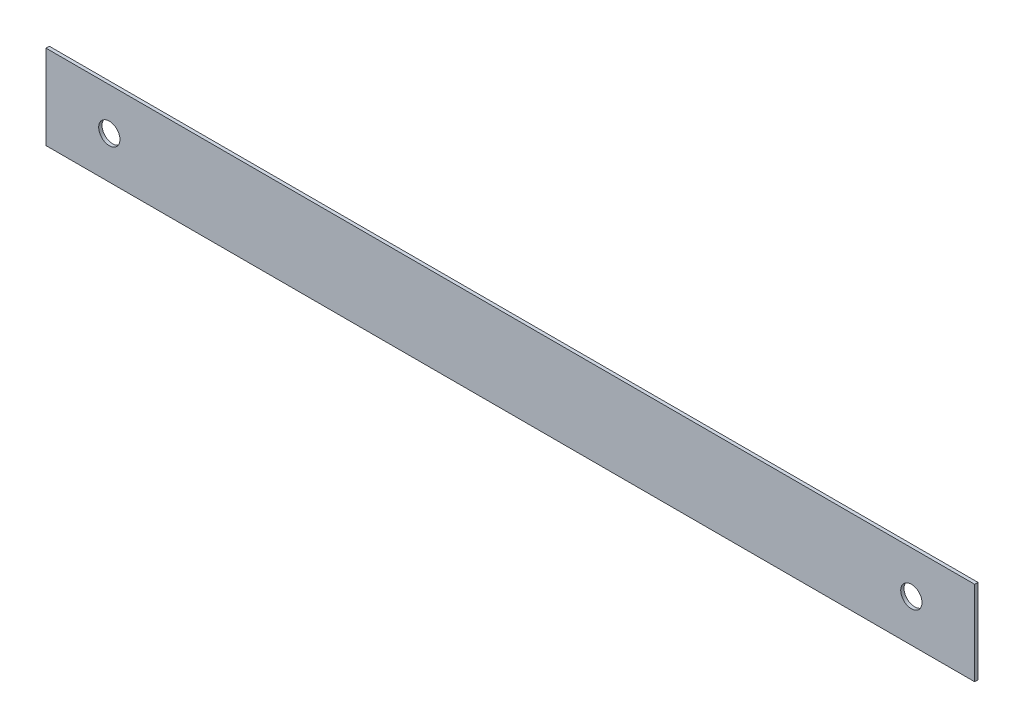
SolidWorks part; units mm, degrees
ref_plane "Front Plane" through (0, 0, 0) normal (0, 0, 1) x (1, 0, 0)
ref_plane "Top Plane" through (0, 0, 0) normal (0, 1, 0) x (1, 0, 0)
ref_plane "Right Plane" through (0, 0, 0) normal (1, 0, 0) x (0, 0, -1)
sketch "Sketch1" plane through (0, 0, 0) normal (0, 0, 1) x (1, 0, 0)
  line L0 (-9.525, -6.35) -> (130.175, -6.35)
  line L1 (130.175, -6.35) -> (130.175, 6.35)
  line L2 (130.175, 6.35) -> (-9.525, 6.35)
  line L3 (-9.525, 6.35) -> (-9.525, -6.35)
  circle A0 centre (0, 0) radius 1.6
  circle A1 centre (120.65, 0) radius 1.6
extrude "Boss-Extrude1" add sketch "Sketch1" along normal blind 0.5
ref_axis "PinRear" through (0, 0, 0.525) along (0, 0, -1)
ref_plane "PinFront_px" through (120.65, 0, 0) normal (1, 0, 0) x (0, 0, -1)
ref_axis "PinFront" through (120.65, 0, 0.525) along (0, 0, -1)
